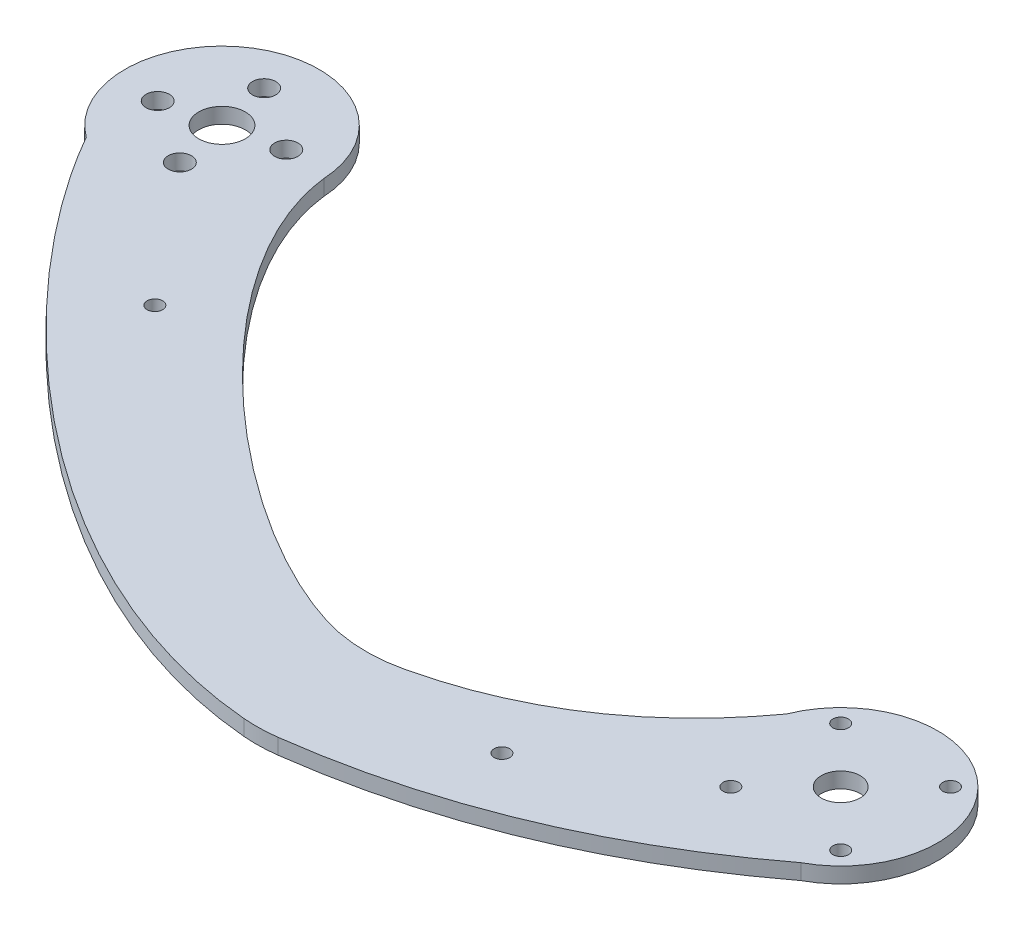
SolidWorks part; units mm, degrees
material "1060 Alloy"
ref_plane "Front" through (0, 0, 0) normal (0, 0, 1) x (1, 0, 0)
ref_plane "Top" through (0, 0, 0) normal (0, 1, 0) x (1, 0, 0)
ref_plane "Right" through (0, 0, 0) normal (1, 0, 0) x (0, 0, -1)
sketch "Sketch2" plane through (0, 0, 0) normal (0, 1, 0) x (1, 0, 0)
  point P0 (0, 0)
  line B0 (-70.9851, 36.1523) -> (-113.5823, 33.9244)
  arc B1 (5.8927, -11.0239) -> (-11.6176, 4.6132) centre (0, 0) ccw
  arc B2 (-101.0993, 34.5773) -> (-120.9882, 23.8546) centre (-113.5823, 33.9244) ccw
  spline B3 degree 3 poles (-44.5149, -15.6481) (-60.4932, -16.621) (-98.7194, 13.994) (-101.0993, 34.5773) knots 0 0 0 0 1 1 1 1
  spline B4 degree 2 poles (5.8927, -11.0239) (-16.2083, -27.8197) (-43.715, -30.9419) knots 0 0 0 1 1 1
  spline B5 degree 3 poles (-43.715, -30.9419) (-74.6559, -29.7722) (-107.9347, 0.9093) (-120.9882, 23.8546) knots 0 0 0 0 1 1 1 1
  spline B6 degree 2 poles (-44.5149, -15.6481) (-23.755, -12.0499) (-11.6176, 4.6132) knots 0 0 0 1 1 1
sketch_block_instance "Block5-1"
sketch_block "Block5" parameters "D1"=25, "D14"=79.1954, "D15"=48.0238, "D17"=92.8889, "D18"=42.1388, "D19"=62.1612, "D2"=5.3089, "D3"=16.6697, "D4"=25.1002, "D5"=50.5803, "D6"=74.3089, "D7"=104.4643, "D8"=116.9643, "D9"=124.8861, "D10"=135.8089, "D11"=34.5967, "D12"=39.8104, "D13"=51.127, "D16"=68.4269
extrude "Boss-Extrude1" add sketch "Sketch2" along normal blind 2 contours B5 B4 B1 B6 B3 B2 region at (-18.1336, 0, 22.9214)
fillet "Fillet2" radius 20 1 edges at (-44.5149, 1, 15.6481)
fillet "Fillet3" radius 20 1 edges at (-43.715, 1, 30.9419)
ref_plane "Plane1" through (0, 2, 0) normal (0, 1, 0) x (1, 0, 0)
sketch "Sketch3" plane through (0, 2, 0) normal (0, 1, 0) x (1, 0, 0)
  line L0 (0, 0) -> (0, 56.3072) construction
  line L1 (-7.0711, 7.0711) -> (0, 0) construction
  line L2 (-113.5823, 33.9244) -> (0, 0) construction
  line L3 (-56.7911, 16.9622) -> (-30.8992, 103.6508) construction
  line L4 (-103.7915, 35.9592) -> (-113.5823, 33.9244) construction
  line L5 (-115.6171, 43.7152) -> (-113.5823, 33.9244) construction
  line L6 (-103.7915, 35.9592) -> (-113.5823, 33.9244) construction
  line L7 (-111.5474, 24.1336) -> (-113.5823, 33.9244) construction
  line L8 (-123.3731, 31.8896) -> (-113.5823, 33.9244) construction
  circle A0 centre (0, 0) radius 2.5
  circle A1 centre (-7.0711, 7.0711) radius 1
  circle A2 centre (7.0711, 7.0711) radius 1
  circle A3 centre (7.0711, -7.0711) radius 1
  circle A4 centre (-7.0711, -7.0711) radius 1
  circle A5 centre (-113.5823, 33.9244) radius 3
  circle A6 centre (-106.7287, 35.3488) radius 1.5
  circle A7 centre (-112.1579, 27.0709) radius 1.5
  circle A8 centre (-120.4358, 32.5001) radius 1.5
  circle A10 centre (-115.0066, 40.778) radius 1.5
  point P8 (-56.7911, 16.9622)
  point P15 (0, 0)
  point P35 (-113.5823, 33.9244)
  dimension "D1" = 5
  dimension "D2" = 2
  dimension "D6" = 6
  dimension "D7" = 3
  dimension "D8" = 7
  dimension "D3" = 45
  dimension "D4" = 10
  dimension "D5" = 4
  dimension "D9" = 4
extrude "Cut-Extrude2" cut sketch "Sketch3" against normal blind 10
sketch "Sketch4" plane through (0, 2, 0) normal (0, 1, 0) x (1, 0, 0)
  line L0 (-113.5823, 33.9244) -> (-69.4661, -34.4033) construction
  line L1 (0, 0) -> (-63.0101, -44.4968) construction
  circle A0 centre (-97.8402, 9.543) radius 1
  circle A1 centre (-25.5617, -18.0513) radius 1
  dimension "D1" = 2
  dimension "D2" = 25.5617
  dimension "D3" = 97.8402
  dimension "D4" = 9.543
  dimension "D5" = 18.0513
extrude "Cut-Extrude3" cut sketch "Sketch4" against normal blind 10
